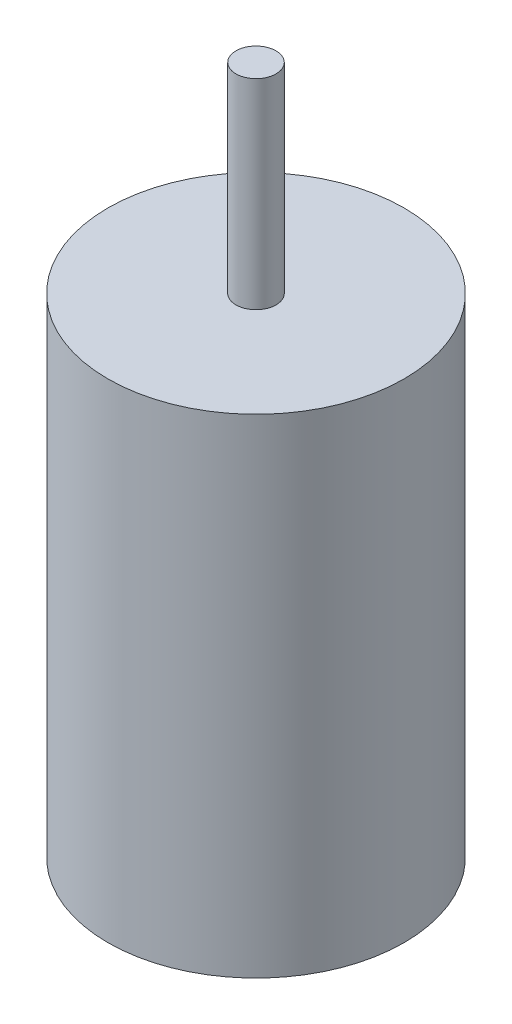
SolidWorks part; units mm, degrees
ref_plane "Front Plane" through (0, 0, 0) normal (0, 0, 1) x (1, 0, 0)
ref_plane "Top Plane" through (0, 0, 0) normal (0, 1, 0) x (1, 0, 0)
ref_plane "Right Plane" through (0, 0, 0) normal (1, 0, 0) x (0, 0, -1)
sketch "Sketch1" plane through (0, 0, 0) normal (0, 1, 0) x (1, 0, 0)
  circle A0 centre (0, 0) radius 18.5
  dimension "D1" = 37
extrude "Boss-Extrude1" add sketch "Sketch1" along normal blind 61
sketch "Sketch2" plane through (0, 61, 0) normal (0, 1, 0) x (1, 0, 0)
  circle A0 centre (0, 0) radius 2.5
  dimension "D1" = 5
extrude "Boss-Extrude2" add sketch "Sketch2" along normal blind 25
